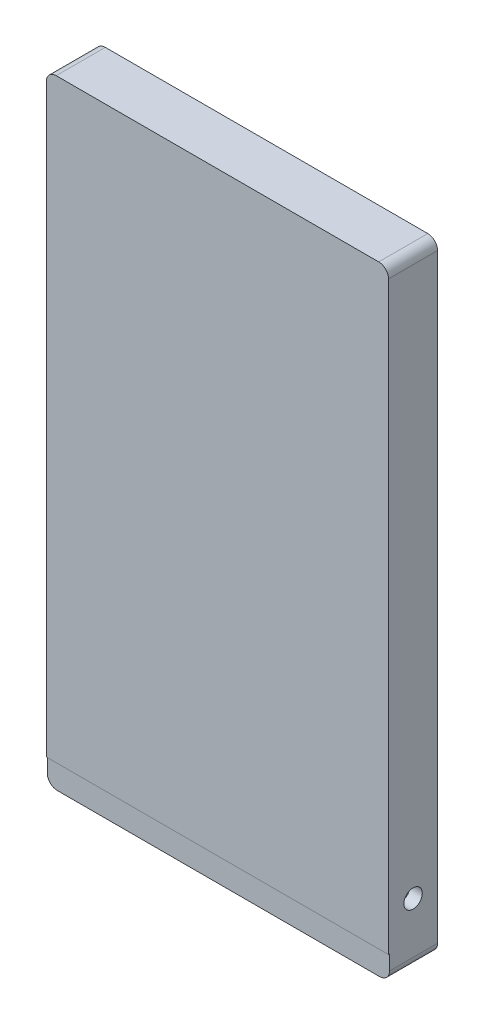
SolidWorks part; units mm, degrees
ref_plane "Front Plane" through (0, 0, 0) normal (0, 0, 1) x (1, 0, 0)
ref_plane "Top Plane" through (0, 0, 0) normal (0, 1, 0) x (1, 0, 0)
ref_plane "Right Plane" through (0, 0, 0) normal (1, 0, 0) x (0, 0, -1)
sketch "Sketch2" plane through (0, 0, 0) normal (0, 0, 1) x (1, 0, 0)
  line L0 (-3.175, -3.175) -> (-3.175, 150.749)
  line L1 (0, 0) -> (82.169, 0)
  line L2 (0, 0) -> (0, 147.574)
  line L3 (0, 147.574) -> (82.169, 147.574)
  line L4 (82.169, 0) -> (82.169, 147.574)
  line L5 (-3.175, 150.749) -> (85.344, 150.749)
  line L6 (85.344, -3.175) -> (85.344, 150.749)
  line L7 (-3.175, -3.175) -> (85.344, -3.175)
  dimension "D1" = 147.574
  dimension "D2" = 82.169
  dimension "D3" = 3.175
extrude "Boss-Extrude2" add sketch "Sketch2" along normal blind 12.7 contours L0 L5 L6 L7
extrude "Cut-Extrude1" cut sketch "Sketch2<6>" along normal blind 10.16 contours L1 L4 L3 L2 region at (41.0845, 73.787, 0)
sketch "Sketch2<6>" plane through (0, 0, 0) normal (0, 0, 1) x (1, 0, 0) same geometry as "Sketch2"
sketch "Sketch3" plane through (85.344, 0, 0) normal (1, 0, 0) x (0, 0, -1)
  circle A0 centre (-6.35, 6.218) radius 2.3813
extrude "Cut-Extrude2" cut sketch "Sketch3" against normal blind 129.54
sketch "Sketch4" plane through (0, -3.175, 0) normal (0, -1, 0) x (1, 0, 0)
  line L0 (-3.175, 12.7) -> (-3.175, 0) construction
  line L1 (-3.175, 12.4478) -> (85.344, 12.4478)
  line L2 (-3.175, 12.4478) -> (-3.175, 0)
  line L3 (-3.175, 0) -> (85.344, 0)
  line L4 (85.344, 12.4478) -> (85.344, 0)
extrude "Boss-Extrude3" add sketch "Sketch4" along normal blind 6.35
fillet "Fillet1" radius 2.54 4 edges at (85.344, -9.525, 6.2239) (-3.175, -9.525, 6.2239) (-3.175, 150.749, 6.35) (85.344, 150.749, 6.35)
